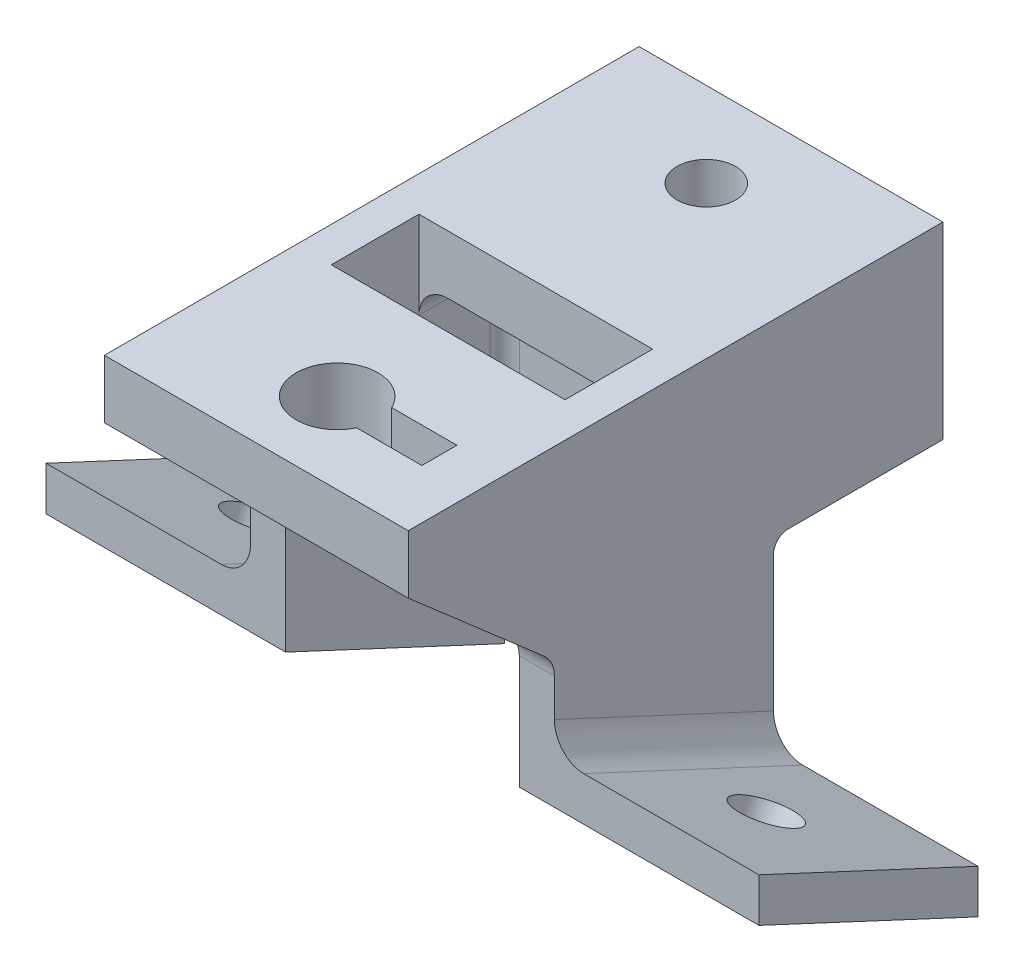
SolidWorks part; units mm, degrees
ref_plane "Front Plane" through (0, 0, 0) normal (0, 0, 1) x (1, 0, 0)
ref_plane "Top Plane" through (0, 0, 0) normal (0, 1, 0) x (1, 0, 0)
ref_plane "Right Plane" through (0, 0, 0) normal (1, 0, 0) x (0, 0, -1)
sketch "Sketch1" plane through (0, 0, 0) normal (0, 1, 0) x (1, 0, 0)
  line L1 (2.032, 2.1971) -> (2.032, -0.8509)
  line L6 (-11.176, -6.35) -> (15.24, -6.35)
  line L7 (-11.176, -6.35) -> (-11.176, 25.4)
  line L8 (-11.176, 25.4) -> (15.24, 25.4)
  line L9 (15.24, -6.35) -> (15.24, 25.4)
  line L15 (2.032, 2.1971) -> (10.922, 2.1971)
  line L16 (2.032, 2.1971) -> (2.032, -0.8509)
  line L17 (2.032, -0.8509) -> (10.922, -0.8509)
  line L18 (10.922, 2.1971) -> (10.922, -0.8509)
  circle A1 centre (2.032, 0.6731) radius 3.556
  point P6 (0, 0)
  point P13 (2.032, 0.6731)
  dimension "D1" = 7.112
  dimension "D2" = 8.89
  dimension "D3" = 13.208
  dimension "D4" = 7.0231
  dimension "D5" = 3.048
  dimension "D8" = 26.416
extrude "Boss-Extrude1" add sketch "Sketch1" along normal blind 5.08
sketch "Sketch2" plane through (0, 5.08, 0) normal (0, 1, 0) x (1, 0, 0)
  line L0 (15.24, -6.35) -> (15.24, 25.4) construction
  line L1 (-8.128, 17.9451) -> (8.382, 17.9451)
  line L2 (-8.128, 17.9451) -> (-8.128, 10.3251)
  line L3 (-8.128, 10.3251) -> (8.382, 10.3251)
  line L4 (8.382, 17.9451) -> (8.382, 10.3251)
  line L5 (-11.176, -6.35) -> (-11.176, 25.4) construction
  line L6 (8.382, 17.9451) -> (12.192, 17.9451)
  line L7 (8.382, 17.9451) -> (8.382, 10.3251)
  line L8 (8.382, 10.3251) -> (12.192, 10.3251)
  line L9 (12.192, 17.9451) -> (12.192, 10.3251)
  arc A0 (5.2449, 2.1971) -> (5.2449, -0.8509) centre (2.032, 0.6731) ccw construction
  dimension "D4" = 7.62
  dimension "D1" = 16.51
  dimension "D2" = 3.048
  dimension "D3" = 9.652
  dimension "D5" = 3.048
extrude "Cut-Extrude1" cut sketch "Sketch2" against normal blind 5.08 contours L4 L1 L2 L3 | L9 L6 L4 L8
sketch "Sketch3" plane through (-11.176, 0, 0) normal (-1, 0, 0) x (0, 0, 1)
  line L1 (-25.4, -22.098) -> (-25.4, -30.9812)
  line L4 (-25.4, -30.9812) -> (-6.35, -22.098)
  line L5 (-25.4, 0) -> (-6.35, 0)
  line L6 (-25.4, 0) -> (-25.4, -22.098)
  line L7 (-25.4, -22.098) -> (-6.35, -22.098)
  line L8 (-6.35, 0) -> (-6.35, -22.098)
  line M2 (-25.4, 0) -> (6.35, 0)
  dimension "D1" = 19.05
  dimension "D2" = 25
  dimension "D3" = 22.098
extrude "Boss-Extrude2" add sketch "Sketch3" against normal blind 26.416 contours L8 L6 L7 M2 | L7 L1 L4
sketch "Sketch6" plane through (-11.176, 0, 0) normal (-1, 0, 0) x (0, 0, 1)
  line L0 (6.35, 0) -> (-6.35, -11.049)
  line L1 (-6.35, 0) -> (-6.35, -22.098) construction
  line L2 (-6.35, -11.049) -> (-6.35, 0)
  line L3 (-6.35, 0) -> (6.35, 0)
extrude "Boss-Extrude3" add sketch "Sketch6" against normal blind 3.048
sketch "Sketch7" plane through (15.24, 0, 0) normal (1, 0, 0) x (0, 0, -1)
  line L0 (-6.35, 0) -> (6.35, -11.049)
  line L1 (6.35, 0) -> (6.35, -22.098) construction
  line L2 (6.35, -11.049) -> (6.35, 0)
  line L3 (6.35, 0) -> (-6.35, 0)
extrude "Boss-Extrude4" add sketch "Sketch7" against normal blind 3.048
sketch "Sketch8" plane through (15.24, 0, 0) normal (1, 0, 0) x (0, 0, -1)
  line L0 (6.35, -22.098) -> (25.4, -30.9812)
  line L1 (25.4, -30.9812) -> (25.4, -27.1712)
  line L2 (25.4, 5.08) -> (25.4, -30.9812) construction
  line L3 (25.4, -27.1712) -> (6.35, -18.288)
  line L4 (6.35, -11.049) -> (6.35, -22.098) construction
  line L5 (6.35, -18.288) -> (6.35, -22.098)
  dimension "D1" = 3.81
extrude "Boss-Extrude5" add sketch "Sketch8" along normal blind 17.78
sketch "Sketch9" plane through (-11.176, 0, 0) normal (-1, 0, 0) x (0, 0, 1)
  line L0 (-6.35, -22.098) -> (-25.4, -30.9812)
  line L1 (-25.4, -30.9812) -> (-25.4, -27.1712)
  line L2 (-25.4, 5.08) -> (-25.4, -30.9812) construction
  line L3 (-25.4, -27.1712) -> (-6.35, -18.288)
  line L4 (-6.35, -11.049) -> (-6.35, -22.098) construction
  line L5 (-6.35, -18.288) -> (-6.35, -22.098)
  dimension "D1" = 3.81
extrude "Boss-Extrude6" add sketch "Sketch9" along normal blind 17.78
sketch "Sketch10" plane through (0, -12.5895, 5.8706) normal (0, 0.9063, -0.4226) x (1, 0, 0)
  line L0 (-28.956, 13.4839) -> (-28.956, 34.5032) construction
  line L1 (33.02, 34.5032) -> (33.02, 13.4839) construction
  line L2 (33.02, 13.4839) -> (15.24, 13.4839) construction
  line L3 (-28.956, 13.4839) -> (-11.176, 13.4839) construction
  circle A0 centre (24.13, 23.9935) radius 2.54
  circle A1 centre (-20.066, 23.9935) radius 2.54
  dimension "D1" = 8.89
  dimension "D2" = 8.89
  dimension "D3" = 10.5096
  dimension "D4" = 10.5096
extrude "Cut-Extrude3" cut sketch "Sketch10" against normal blind 17.78
sketch "Sketch11" plane through (0, 0, -25.4) normal (0, 0, -1) x (-1, 0, 0)
  line L0 (-15.24, 5.08) -> (-15.24, -27.1712) construction
  line L1 (-12.192, 0) -> (8.128, 0)
  line L2 (-12.192, 0) -> (-12.192, -30.9812)
  line L3 (-12.192, -30.9812) -> (8.128, -30.9812)
  line L4 (8.128, 0) -> (8.128, -30.9812)
  line L5 (11.176, 5.08) -> (-15.24, 5.08) construction
  line L6 (-33.02, -30.9812) -> (28.956, -30.9812) construction
  dimension "D1" = 20.32
  dimension "D2" = 3.048
  dimension "D3" = 5.08
  dimension "D4" = 0
extrude "Cut-Extrude4" cut sketch "Sketch11" against normal blind 22.86
fillet "Fillet3" radius 2.54 4 edges at (-8.128, 0, -21.6726) (12.192, 0, -21.6726) (15.24, -22.7296, -15.875) (-11.176, -22.7296, -15.875)
fillet "Fillet4" radius 2.54 2 edges at (-9.652, -11.049, -6.35) (13.716, -11.049, -6.35)
sketch "Sketch12" plane through (0, 5.08, 0) normal (0, 1, 0) x (1, 0, 0)
  line L1 (-11.176, 25.4) -> (15.24, 25.4)
  line L2 (-11.176, 25.4) -> (-11.176, 40.132)
  line L3 (-11.176, 40.132) -> (15.24, 40.132)
  line L4 (15.24, 25.4) -> (15.24, 40.132)
  circle A0 centre (2.032, 32.766) radius 2.54
  dimension "D5" = 5.08
  dimension "D1" = 26.416
  dimension "D2" = 14.732
  dimension "D3" = 13.208
  dimension "D4" = 7.366
extrude "Boss-Extrude7" add sketch "Sketch12" against normal blind 16.383
fillet "Fillet5" radius 1.27 5 edges at (-8.128, -6.9215, -25.4) (-7.3841, -0.7439, -25.4) (11.4481, -0.7439, -25.4) (12.192, -6.9215, -25.4) (2.032, 0, -25.4)
fillet "Fillet6" radius 1.27 2 edges at (-9.652, -11.303, -25.4) (13.716, -11.303, -25.4)
